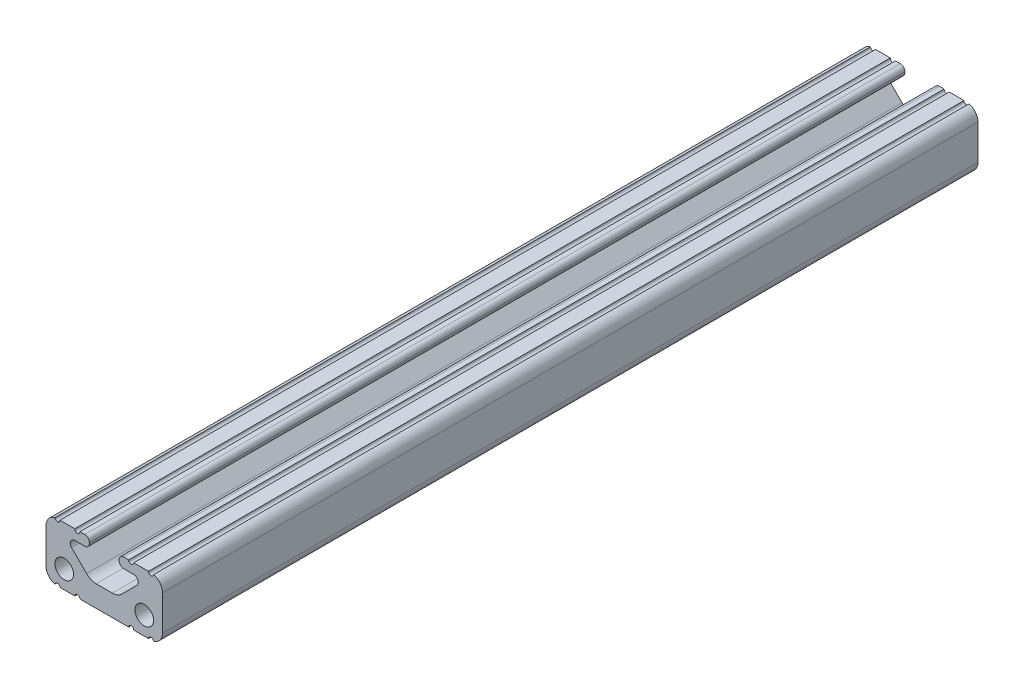
SolidWorks part; units mm, degrees
ref_plane "Front Plane" through (0, 0, 0) normal (0, 0, 1) x (1, 0, 0)
ref_plane "Top Plane" through (0, 0, 0) normal (0, 1, 0) x (1, 0, 0)
ref_plane "Right Plane" through (0, 0, 0) normal (1, 0, 0) x (0, 0, -1)
sketch "Sketch1" plane through (0, 0, 0) normal (0, 0, 1) x (1, 0, 0)
  line L0 (0, 6.35) -> (0, -6.35) construction
  line L1 (0, -6.35) -> (12.7, -6.35)
  line L2 (12.7, -6.35) -> (12.7, 6.35)
  line L3 (12.7, 6.35) -> (3.2512, 6.35)
  line L4 (3.2512, 6.35) -> (3.2512, 4.1402)
  line L5 (3.2512, 4.1402) -> (6.4224, 4.1402)
  line L6 (7.1255, 2.4426) -> (2.9811, -1.7018)
  line L7 (2.9811, -1.7018) -> (0, -1.7018)
  circle A0 centre (8.7249, -2.3876) radius 2.032
  arc A1 (6.4224, 4.1402) -> (7.1255, 2.4426) centre (6.4224, 3.1458) cw
  dimension "Center Hole Diameter" = 4.064
  dimension "D3" = 0.9944
  dimension "Rail Height" = 25.4
  dimension "Rail Width" = 12.7
  dimension "Hole CtoC" = 17.4498
  dimension "D1" = 3.9624
  dimension "T-Slot Width" = 6.5024
  dimension "Thickness" = 2.2098
  dimension "Inner Slot Width" = 14.8336
  dimension "Slot Depth" = 5.842
  dimension "D2" = 45
sketch "Sketch2" plane through (0, 0, 0) normal (1, 0, 0) x (0, 0, -1)
  line L0 (-152.4, -6.35) -> (152.4, -6.35) construction
  line L1 (-127, 0) -> (127, 0) construction
  dimension "Length" = 304.8
sketch "Sketch3" plane through (0, 0, 0) normal (0, 0, 1) x (1, 0, 0)
  line L0 (3.2512, 6.35) -> (3.2512, 4.1402) construction
  line L1 (12.7, 6.35) -> (3.2512, 6.35) construction
  line L2 (3.2512, 4.1402) -> (6.4224, 4.1402) construction
  line L3 (3.2512, 5.3556) -> (3.2512, 5.1346)
  line L4 (12.7, -6.35) -> (12.7, 6.35) construction
  line L5 (0, -6.35) -> (12.7, -6.35) construction
  line L6 (2.9811, -1.7018) -> (0, -1.7018) construction
  line L7 (7.1255, 2.4426) -> (2.9811, -1.7018) construction
  line L8 (0, -1.7018) -> (1.7454, -1.7018)
  line L9 (4.2456, 4.1402) -> (6.4224, 4.1402)
  line L10 (3.8549, -0.828) -> (7.1255, 2.4426)
  line L11 (0, -1.7018) -> (0, -6.35)
  line L12 (0, -6.35) -> (10.16, -6.35)
  line L13 (12.7, -3.81) -> (12.7, 3.81)
  line L14 (4.2456, 6.35) -> (10.16, 6.35)
  arc A0 (3.2512, 5.3556) -> (4.2456, 6.35) centre (4.2456, 5.3556) cw
  arc A1 (3.2512, 5.1346) -> (4.2456, 4.1402) centre (4.2456, 5.1346) ccw
  arc A2 (7.1255, 2.4426) -> (6.4224, 4.1402) centre (6.4224, 3.1458) ccw construction
  arc A3 (10.16, 6.35) -> (12.7, 3.81) centre (10.16, 3.81) cw
  arc A4 (10.16, -6.35) -> (12.7, -3.81) centre (10.16, -3.81) ccw
  arc A5 (7.1255, 2.4426) -> (6.4224, 4.1402) centre (6.4224, 3.1458) ccw
  circle A6 centre (8.7249, -2.3876) radius 2.032 construction
  circle A7 centre (8.7249, -2.3876) radius 2.032
  arc A8 (1.7454, -1.7018) -> (3.8549, -0.828) centre (1.7454, 1.2814) ccw
  dimension "D2" = 2.9832
extrude "Boss-Extrude1" add sketch "Sketch3" along normal mid plane 304.8
sketch "Sketch4" plane through (0, 0, 0) normal (0, 0, 1) x (1, 0, 0)
  line L0 (12.7, 6.35) -> (3.2512, 6.35) construction
  line L1 (0, -6.35) -> (12.7, -6.35) construction
  line L2 (10.7569, -2.3876) -> (10.7569, 6.35) construction
  line L3 (6.4224, 3.1458) -> (6.4224, 6.35) construction
  circle A0 centre (5.8699, 6.35) radius 0.5524
  circle A1 centre (10.2045, 6.35) radius 0.5524
  circle A2 centre (5.8699, -6.35) radius 0.5524
  circle A3 centre (10.2045, -6.35) radius 0.5524
  circle A4 centre (8.7249, -2.3876) radius 2.032 construction
  dimension "D1" = 1.1049
extrude "Cut-Extrude1" cut sketch "Sketch4" against normal through all both and the other way through all
mirror "Mirror1" about plane through (0, 0, 0) normal (1, 0, 0) of bodies 135
sketch "Sketch5" plane through (0, 0, 152.4) normal (0, 0, 1) x (1, 0, 0)
  line L16 (9.652, 6.35) -> (6.4224, 6.35)
  line L17 (5.3175, 6.35) -> (4.2456, 6.35)
  line L18 (3.2512, 5.3556) -> (3.2512, 5.1346)
  line L19 (4.2456, 4.1402) -> (6.4224, 4.1402)
  line L20 (7.1255, 2.4426) -> (3.8549, -0.828)
  line L21 (1.7454, -1.7018) -> (-1.7454, -1.7018)
  line L22 (-3.8549, -0.828) -> (-7.1255, 2.4426)
  line L23 (-6.4224, 4.1402) -> (-4.2456, 4.1402)
  line L24 (-3.2512, 5.1346) -> (-3.2512, 5.3556)
  line L25 (-4.2456, 6.35) -> (-5.3175, 6.35)
  line L26 (-6.4224, 6.35) -> (-9.652, 6.35)
  line L27 (-12.7, 3.81) -> (-12.7, -3.81)
  line L28 (-9.652, -6.35) -> (-6.4224, -6.35)
  line L29 (-5.3175, -6.35) -> (5.3175, -6.35)
  line L30 (6.4224, -6.35) -> (9.652, -6.35)
  line L31 (12.7, -3.81) -> (12.7, 3.81)
  line L32 (9.652, 6.35) -> (6.4224, 6.35)
  line L33 (5.3175, 6.35) -> (4.2456, 6.35)
  line L34 (3.2512, 5.3556) -> (3.2512, 5.1346)
  line L35 (4.2456, 4.1402) -> (6.4224, 4.1402)
  line L36 (7.1255, 2.4426) -> (3.8549, -0.828)
  line L37 (1.7454, -1.7018) -> (-1.7454, -1.7018)
  line L38 (-3.8549, -0.828) -> (-7.1255, 2.4426)
  line L39 (-6.4224, 4.1402) -> (-4.2456, 4.1402)
  line L40 (-3.2512, 5.1346) -> (-3.2512, 5.3556)
  line L41 (-4.2456, 6.35) -> (-5.3175, 6.35)
  line L42 (-6.4224, 6.35) -> (-9.652, 6.35)
  line L43 (-12.7, 3.81) -> (-12.7, -3.81)
  line L44 (-9.652, -6.35) -> (-6.4224, -6.35)
  line L45 (-5.3175, -6.35) -> (5.3175, -6.35)
  line L46 (6.4224, -6.35) -> (9.652, -6.35)
  line L47 (12.7, -3.81) -> (12.7, 3.81)
  arc A20 (12.7, 3.81) -> (10.7524, 6.2799) centre (10.16, 3.81) ccw
  arc A21 (9.652, 6.35) -> (10.7524, 6.2799) centre (10.2045, 6.35) ccw
  arc A22 (5.3175, 6.35) -> (6.4224, 6.35) centre (5.8699, 6.35) ccw
  arc A23 (4.2456, 6.35) -> (3.2512, 5.3556) centre (4.2456, 5.3556) ccw
  arc A24 (3.2512, 5.1346) -> (4.2456, 4.1402) centre (4.2456, 5.1346) ccw
  arc A25 (7.1255, 2.4426) -> (6.4224, 4.1402) centre (6.4224, 3.1458) ccw
  arc A26 (1.7454, -1.7018) -> (3.8549, -0.828) centre (1.7454, 1.2814) ccw
  arc A27 (-3.8549, -0.828) -> (-1.7454, -1.7018) centre (-1.7454, 1.2814) ccw
  arc A28 (-6.4224, 4.1402) -> (-7.1255, 2.4426) centre (-6.4224, 3.1458) ccw
  arc A29 (-4.2456, 4.1402) -> (-3.2512, 5.1346) centre (-4.2456, 5.1346) ccw
  arc A30 (-3.2512, 5.3556) -> (-4.2456, 6.35) centre (-4.2456, 5.3556) ccw
  arc A31 (-6.4224, 6.35) -> (-5.3175, 6.35) centre (-5.8699, 6.35) ccw
  arc A32 (-10.7524, 6.2799) -> (-9.652, 6.35) centre (-10.2045, 6.35) ccw
  arc A33 (-10.7524, 6.2799) -> (-12.7, 3.81) centre (-10.16, 3.81) ccw
  arc A34 (-12.7, -3.81) -> (-10.7524, -6.2799) centre (-10.16, -3.81) ccw
  arc A35 (-9.652, -6.35) -> (-10.7524, -6.2799) centre (-10.2045, -6.35) ccw
  arc A36 (-5.3175, -6.35) -> (-6.4224, -6.35) centre (-5.8699, -6.35) ccw
  arc A37 (6.4224, -6.35) -> (5.3175, -6.35) centre (5.8699, -6.35) ccw
  arc A38 (10.7524, -6.2799) -> (9.652, -6.35) centre (10.2045, -6.35) ccw
  arc A39 (10.7524, -6.2799) -> (12.7, -3.81) centre (10.16, -3.81) ccw
  arc A40 (12.7, 3.81) -> (10.7524, 6.2799) centre (10.16, 3.81) ccw
  arc A41 (9.652, 6.35) -> (10.7524, 6.2799) centre (10.2045, 6.35) ccw
  arc A42 (5.3175, 6.35) -> (6.4224, 6.35) centre (5.8699, 6.35) ccw
  arc A43 (4.2456, 6.35) -> (3.2512, 5.3556) centre (4.2456, 5.3556) ccw
  arc A44 (3.2512, 5.1346) -> (4.2456, 4.1402) centre (4.2456, 5.1346) ccw
  arc A45 (7.1255, 2.4426) -> (6.4224, 4.1402) centre (6.4224, 3.1458) ccw
  arc A46 (1.7454, -1.7018) -> (3.8549, -0.828) centre (1.7454, 1.2814) ccw
  arc A47 (-3.8549, -0.828) -> (-1.7454, -1.7018) centre (-1.7454, 1.2814) ccw
  arc A48 (-6.4224, 4.1402) -> (-7.1255, 2.4426) centre (-6.4224, 3.1458) ccw
  arc A49 (-4.2456, 4.1402) -> (-3.2512, 5.1346) centre (-4.2456, 5.1346) ccw
  arc A50 (-3.2512, 5.3556) -> (-4.2456, 6.35) centre (-4.2456, 5.3556) ccw
  arc A51 (-6.4224, 6.35) -> (-5.3175, 6.35) centre (-5.8699, 6.35) ccw
  arc A52 (-10.7524, 6.2799) -> (-9.652, 6.35) centre (-10.2045, 6.35) ccw
  arc A53 (-10.7524, 6.2799) -> (-12.7, 3.81) centre (-10.16, 3.81) ccw
  arc A54 (-12.7, -3.81) -> (-10.7524, -6.2799) centre (-10.16, -3.81) ccw
  arc A55 (-9.652, -6.35) -> (-10.7524, -6.2799) centre (-10.2045, -6.35) ccw
  arc A56 (-5.3175, -6.35) -> (-6.4224, -6.35) centre (-5.8699, -6.35) ccw
  arc A57 (6.4224, -6.35) -> (5.3175, -6.35) centre (5.8699, -6.35) ccw
  arc A58 (10.7524, -6.2799) -> (9.652, -6.35) centre (10.2045, -6.35) ccw
  arc A59 (10.7524, -6.2799) -> (12.7, -3.81) centre (10.16, -3.81) ccw
  dimension "D1" = 0
extrude "Cut-Extrude2" cut sketch "Sketch5" against normal offset from surface (127 mm away) 177.8 up to face at (0, 1.3921, -152.4)
equation "\"D3@Sketch1\"=\"Thickness@Sketch1\"*0.45"
equation "\"D1@Sketch3\"=\"Rail Width@Sketch1\"*0.2"
equation "\"D2@Sketch3\"=\"D3@Sketch1\"*3"
equation "\"D1@Boss-Extrude1\"=\"length@sketch2\""
equation "\"D1@Sketch4\"=\"Thickness@Sketch1\"*0.5"
